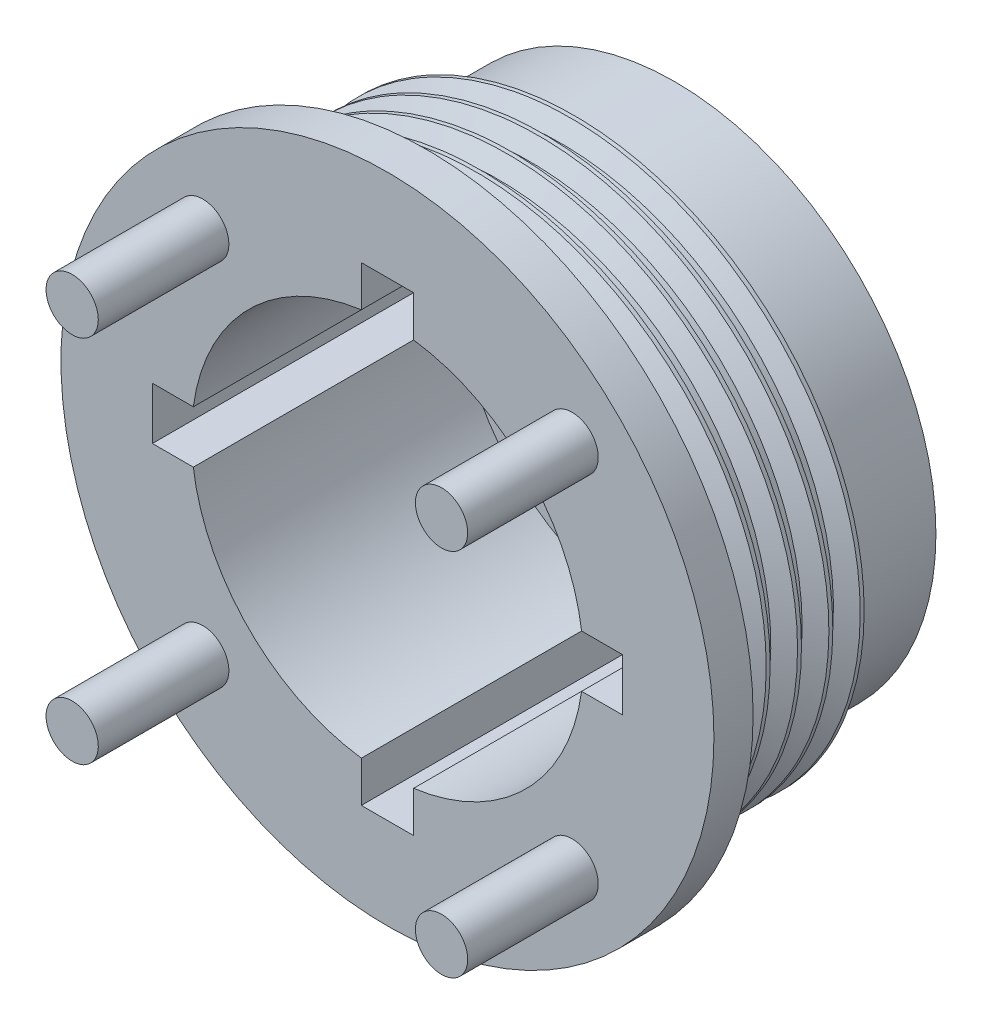
SolidWorks part; units mm, degrees
ref_plane "Ön Düzlem" through (0, 0, 0) normal (0, 0, 1) x (1, 0, 0)
ref_plane "Üst Düzlem" through (0, 0, 0) normal (0, 1, 0) x (1, 0, 0)
ref_plane "Sağ Düzlem" through (0, 0, 0) normal (1, 0, 0) x (0, 0, -1)
sketch "Sketch1" plane through (0, 0, 0) normal (0, 0, 1) x (1, 0, 0)
  circle A0 centre (0, 0) radius 3.75
  circle A1 centre (0, 0) radius 6.25
  dimension "D1" = 7.5
  dimension "D2" = 12.5
extrude "Boss-Extrude1" add sketch "Sketch1" along normal blind 5
sketch "Sketch2" plane through (0, 0, 0) normal (0, 0, -1) x (-1, 0, 0)
  circle A0 centre (0, 0) radius 3.75
  circle A1 centre (0, 0) radius 5.5
  dimension "D1" = 11
  dimension "D2" = 7.5
extrude "Boss-Extrude2" add sketch "Sketch2" along normal blind 3
thread "Thread1" pitch 0.6 method cut profile "Thread Profile1" start angle 0, offset 1, length 4, pitch 0.6, diameter 11
ref_plane "Plane1" through (5.5, 0, -4) normal (0, -1, 0) x (1, 0, 0)
sketch "Thread Profile1" plane through (5.5, 0, -4) normal (0, -1, 0) x (1, 0, 0)
  line L0 (0, 0) -> (0, 0.6) construction
  line L11 (0, 0) -> (0, 0.525)
  line L12 (0, 0.525) -> (-0.3248, 0.3375)
  line L13 (-0.3248, 0.3375) -> (-0.3248, 0.1875)
  line L15 (-0.3248, 0.1875) -> (0, 0)
  line L17 (-0.3248, 0.2625) -> (0, 0.2625) construction
  point P2 (0, 0)
  dimension "Pitch" = 0.6
  dimension "Profile_Angle" = 60
  dimension "Profile_Land" = 0.15
  dimension "Profile_Height" = 0.3248
sketch "Sketch5" plane through (0, 0, -3) normal (0, 0, -1) x (-1, 0, 0)
  line L0 (4.5, 0.5) -> (3.5, 0.5)
  line L1 (-0.5, 4.5) -> (0.5, 4.5)
  line L2 (-0.5, 4.5) -> (-0.5, 3.5)
  line L3 (-0.5, 3.5) -> (0.5, 3.5)
  line L4 (0.5, 4.5) -> (0.5, 3.5)
  line L5 (4.5, 0.5) -> (4.5, -0.5)
  line L6 (4.5, -0.5) -> (3.5, -0.5)
  line L7 (3.5, 0.5) -> (3.5, -0.5)
  line L8 (0.5, -4.5) -> (0.5, -3.5)
  line L9 (0.5, -4.5) -> (-0.5, -4.5)
  line L10 (-0.5, -4.5) -> (-0.5, -3.5)
  line L11 (0.5, -3.5) -> (-0.5, -3.5)
  line L12 (-4.5, -0.5) -> (-3.5, -0.5)
  line L13 (-4.5, -0.5) -> (-4.5, 0.5)
  line L14 (-4.5, 0.5) -> (-3.5, 0.5)
  line L15 (-3.5, -0.5) -> (-3.5, 0.5)
  point P4 (0, 3.5)
  point P21 (0, 0)
  dimension "D1" = 1
  dimension "D2" = 1
  dimension "D3" = 3.5
  dimension "D4" = 4
sketch "Sketch7" plane through (0, 0, -3) normal (0, 0, -1) x (-1, 0, 0)
  circle A0 centre (0, 0) radius 3.75
  circle A1 centre (0, 0) radius 5
  dimension "D1" = 7.5
  dimension "D2" = 10
extrude "Boss-Extrude3" add sketch "Sketch7" along normal blind 1.25
extrude "Cut-Extrude3" cut sketch "Sketch5" against normal blind 5.5 and the other way blind 6.5
sketch "Sketch8" plane through (0, 0, -4.25) normal (0, 0, -1) x (-1, 0, 0)
  circle A0 centre (0, 0) radius 3
  circle A1 centre (0, 0) radius 5
  dimension "D1" = 10
  dimension "D2" = 6
extrude "Boss-Extrude4" add sketch "Sketch8" along normal blind 0.5
sketch "Sketch9" plane through (0, 0, 0) normal (0, 1, 0) x (1, 0, 0)
  line L0 (6.25, 0) -> (-6.25, 0) construction
  line L1 (-17.34, -0.75) -> (21.395, -0.75)
  line L2 (-17.34, -0.75) -> (-17.34, -9.8255)
  line L3 (-17.34, -9.8255) -> (21.395, -9.8255)
  line L4 (21.395, -0.75) -> (21.395, -9.8255)
  dimension "D1" = 0.75
extrude "Cut-Extrude4" cut sketch "Sketch9" against normal blind 10 and the other way blind 10
sketch "Sketch10" plane through (0, 0, 0.75) normal (0, 0, 1) x (1, 0, 0)
  line L0 (-3.5355, 3.5355) -> (0, 0) construction
  line L1 (0, 0) -> (-10, 0) construction
  circle A0 centre (-3.5355, 3.5355) radius 0.5
  dimension "D4" = 1
  dimension "D1" = 10
  dimension "D2" = 45
  dimension "D3" = 5
extrude "Boss-Extrude5" add sketch "Sketch10" along normal blind 2.5
pattern_circular "CirPattern1" count 4 over 360 about axis through (0, 0, 5) along (0, 0, -1) of "Boss-Extrude5" reverse direction yes
sketch "Sketch11" plane through (0, 0, -4.25) normal (0, 0, 1) x (1, 0, 0)
  line L0 (-4.5, -0.5) -> (-3.7165, -0.5) construction
  line L1 (-0.5, 4.5) -> (0.5, 4.5)
  line L2 (-0.5, 4.5) -> (-0.5, 3.7165)
  line L4 (0.5, 4.5) -> (0.5, 3.7165)
  line L5 (4.5, -0.5) -> (3.7165, -0.5)
  line L6 (4.5, -0.5) -> (4.5, 0.5)
  line L7 (4.5, 0.5) -> (3.7165, 0.5)
  line L9 (0.5, -4.5) -> (-0.5, -4.5)
  line L10 (0.5, -4.5) -> (0.5, -3.7165)
  line L12 (-0.5, -4.5) -> (-0.5, -3.7165)
  line L13 (-4.5, 0.5) -> (-3.7165, 0.5)
  line L14 (-4.5, 0.5) -> (-4.5, -0.5)
  line L15 (-4.5, -0.5) -> (-3.7165, -0.5)
  line L17 (0.5, 3.7165) -> (0.5, 4.5) construction
  line L18 (4.5, 0.5) -> (3.7165, 0.5) construction
  line L19 (-0.5, -3.7165) -> (-0.5, -4.5) construction
  arc A0 (-3.7165, -0.5) -> (-0.5, -3.7165) centre (0, 0) ccw
  arc A1 (-0.5, 3.7165) -> (-3.7165, 0.5) centre (0, 0) ccw
  arc A2 (3.7165, 0.5) -> (0.5, 3.7165) centre (0, 0) ccw
  arc A3 (0.5, -3.7165) -> (3.7165, -0.5) centre (0, 0) ccw
extrude "Cut-Extrude5" cut sketch "Sketch11" against normal blind 0.1
